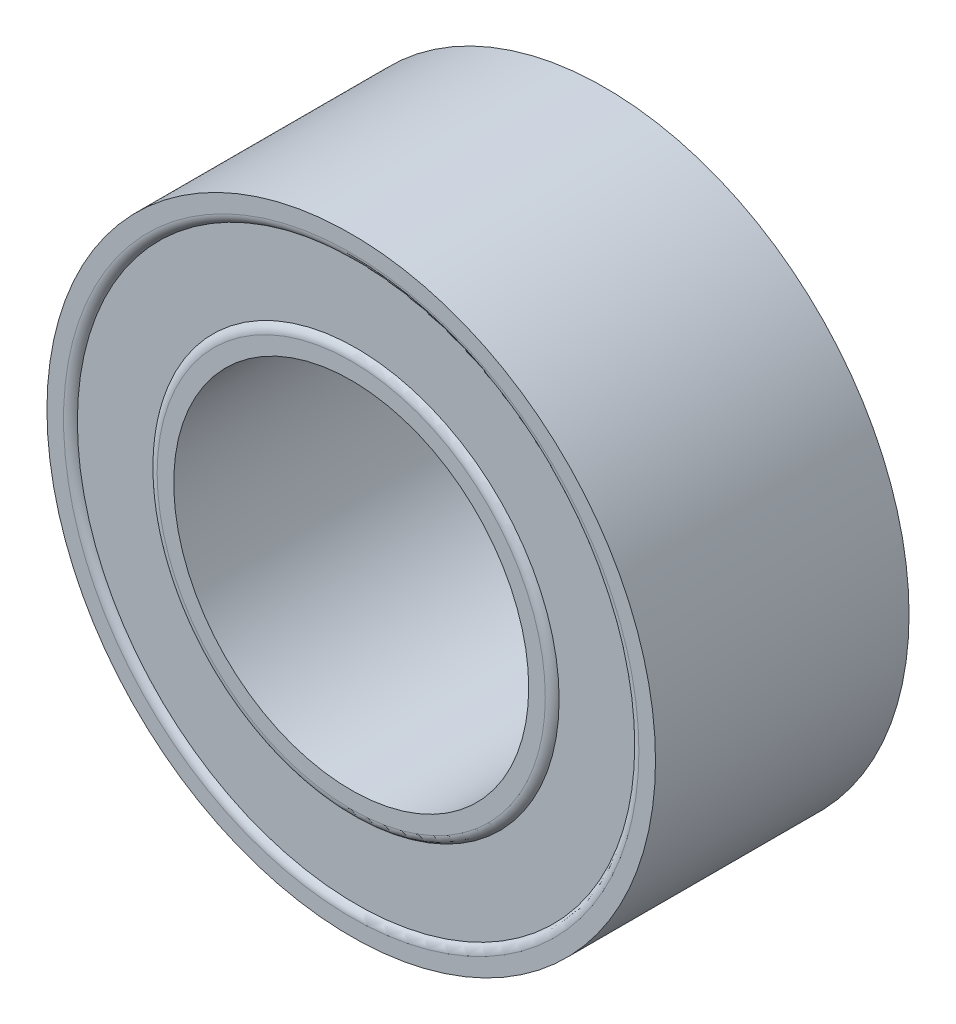
SolidWorks part; units mm, degrees
ref_plane "前视基准面" through (0, 0, 0) normal (0, 0, 1) x (1, 0, 0)
ref_plane "上视基准面" through (0, 0, 0) normal (0, 1, 0) x (1, 0, 0)
ref_plane "右视基准面" through (0, 0, 0) normal (1, 0, 0) x (0, 0, -1)
sketch "草图1" plane through (0, 0, 0) normal (0, 0, 1) x (1, 0, 0)
  circle A0 centre (0, 0) radius 3.5
  circle A1 centre (0, 0) radius 6
  dimension "D1" = 7
  dimension "D2" = 12
extrude "凸台-拉伸1" add sketch "草图1" along normal mid plane 5
sketch "草图2" plane through (0, 0, 2.5) normal (0, 0, 1) x (1, 0, 0)
  circle A0 centre (0, 0) radius 4
  circle A1 centre (0, 0) radius 5.5
  circle A2 centre (0, 0) radius 6 construction
  circle A3 centre (0, 0) radius 3.5 construction
  dimension "D1" = 0.5
  dimension "D2" = 0.5
extrude "切除-拉伸1" cut sketch "草图2" against normal blind 0.1
mirror "镜向1" about plane through (0, 0, 0) normal (0, 0, 1) of "切除-拉伸1"
fillet "圆角1" radius 0.2 4 edges at (5.5, 0, -2.5) (4, 0, -2.5) (5.5, 0, 2.5) (4, 0, 2.5)
